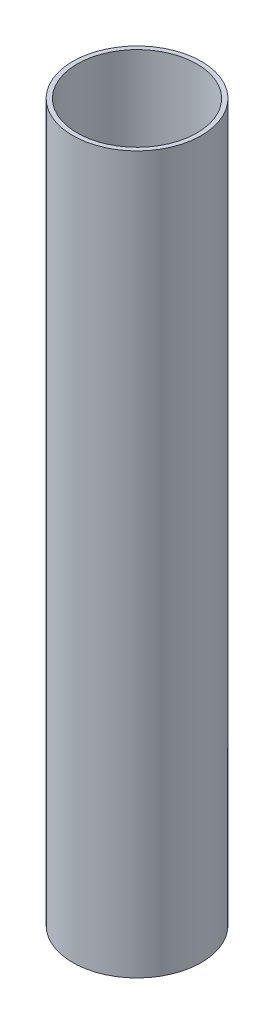
SolidWorks part; units mm, degrees
ref_plane "Front Plane" through (0, 0, 0) normal (0, 0, 1) x (1, 0, 0)
ref_plane "Top Plane" through (0, 0, 0) normal (0, 1, 0) x (1, 0, 0)
ref_plane "Right Plane" through (0, 0, 0) normal (1, 0, 0) x (0, 0, -1)
sketch "Sketch1" plane through (0, 0, 0) normal (0, 0, 1) x (1, 0, 0)
  line L0 (0, 0) -> (0, 304.8) construction
  line L1 (-20.5232, 0) -> (-19.1008, 0)
  line L2 (-20.5232, 0) -> (-20.5232, 228.6)
  line L3 (-20.5232, 228.6) -> (-19.1008, 228.6)
  line L4 (20.5232, 0) -> (20.5232, 228.6)
  line L5 (-19.1008, 0) -> (-19.1008, 228.6)
  line L6 (19.1008, 228.6) -> (19.1008, 0)
  line L7 (19.1008, 0) -> (20.5232, 0)
  line L8 (19.1008, 228.6) -> (20.5232, 228.6)
  dimension "D1" = 41.0464
  dimension "12" = 228.6
  dimension "D2" = 38.2016
revolve "Revolve2" add sketch "Sketch1" angle 360 about L0 region at (-19.812, 114.3, 0)
